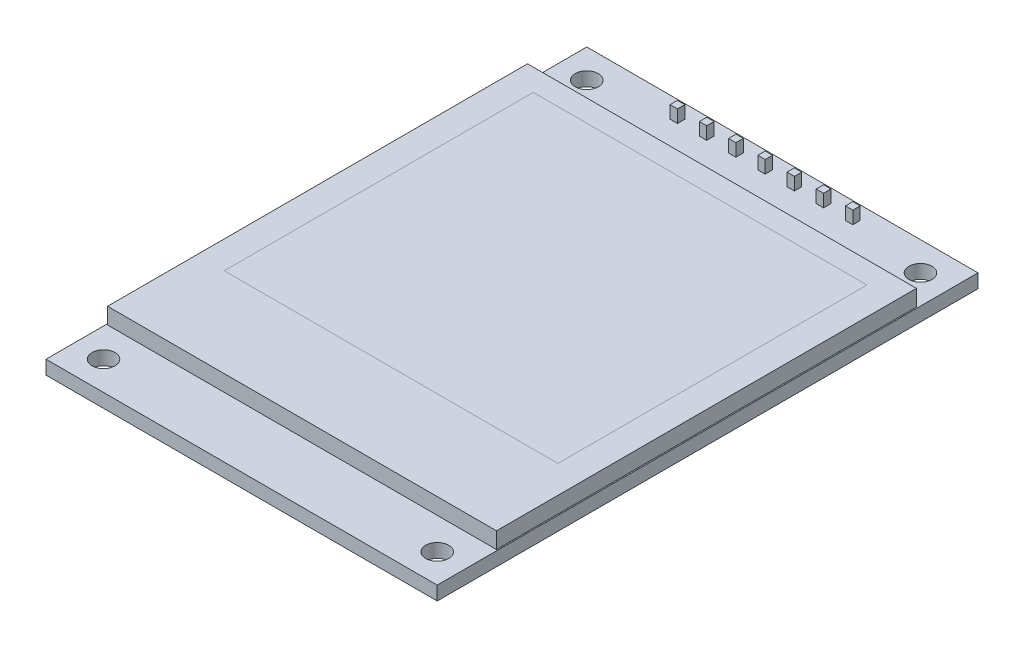
SolidWorks part; units mm, degrees
ref_plane "前视基准面" through (0, 0, 0) normal (0, 0, 1) x (1, 0, 0)
ref_plane "上视基准面" through (0, 0, 0) normal (0, 1, 0) x (1, 0, 0)
ref_plane "右视基准面" through (0, 0, 0) normal (1, 0, 0) x (0, 0, -1)
sketch "PCB底板草图" plane through (0, 0, 0) normal (0, 1, 0) x (1, 0, 0)
  line L1 (-17, -23.5) -> (17, -23.5)
  line L2 (-17, -23.5) -> (-17, 23.5)
  line L3 (-17, 23.5) -> (17, 23.5)
  line L4 (17, -23.5) -> (17, 23.5)
  circle A0 centre (-14.5, 21) radius 1
  circle A1 centre (14.5, 21) radius 1
  circle A4 centre (-14.5, -21) radius 1
  circle A5 centre (14.5, -21) radius 1
  point P0 (0, 0)
extrude "PCB底板" add sketch "PCB底板草图" along normal blind 1.2
sketch "OLED草图" plane through (0, 1.2, 0) normal (0, 1, 0) x (1, 0, 0)
  line L1 (17, 23.5) -> (-17, 23.5) construction
  line L3 (-17, 0) -> (-16.9, 0)
  line L4 (-17, 23.5) -> (-17, -23.5) construction
  line L6 (-16.9, 18.25) -> (-16.9, -18.25)
  line L7 (17, -23.5) -> (17, 23.5) construction
  line L9 (-16.9, -18.25) -> (16.9, -18.25)
  line L11 (16.9, 18.25) -> (16.9, -18.25)
  line L12 (-16.9, 18.25) -> (16.9, 18.25)
  line L13 (-14.5, 16.35) -> (14.5, 16.35)
  line L14 (14.5, 16.35) -> (14.5, -10.51)
  line L15 (-14.5, 16.35) -> (-14.5, -10.51)
  line L16 (-14.5, -10.51) -> (14.5, -10.51)
  dimension "D1" = 0.1
  dimension "D2" = 0.1
  dimension "D3" = 5.25
extrude "OLED屏幕" add sketch "OLED草图" along normal blind 1.41 contours L15 L16 L14 L13 region at (0, 1.2, -2.92)
extrude "OLED黑边" add sketch "OLED草图<3>" along normal blind 1.41 separate body contours L12 L6 L9 L11 L16 L15 L13 L14 region at (0, 1.2, -17.7525)
sketch "OLED草图<3>" plane through (0, 1.2, 0) normal (0, 1, 0) x (1, 0, 0) same geometry as "OLED草图"
sketch "2.54针脚草图" plane through (0, 0, 0) normal (0, -1, 0) x (1, 0, 0)
  line L0 (17, -23.5) -> (-17, -23.5) construction
  line L2 (17, 23.5) -> (17, -23.5) construction
  line L5 (8.89, -20.73) -> (6.35, -20.73)
  line L6 (8.89, -20.73) -> (8.89, -23.27)
  line L7 (8.89, -23.27) -> (6.35, -23.27)
  line L8 (6.35, -20.73) -> (6.35, -23.27)
  line L11 (7.94, -21.68) -> (7.3, -21.68)
  line L12 (7.94, -21.68) -> (7.94, -22.32)
  line L13 (7.94, -22.32) -> (7.3, -22.32)
  line L14 (7.3, -21.68) -> (7.3, -22.32)
  line L17 (5.4, -21.68) -> (4.76, -21.68)
  line L18 (3.81, -20.73) -> (6.35, -20.73)
  line L19 (3.81, -20.73) -> (3.81, -23.27)
  line L20 (3.81, -23.27) -> (6.35, -23.27)
  line L21 (6.35, -20.73) -> (6.35, -23.27)
  line L24 (1.27, -20.73) -> (3.81, -20.73)
  line L25 (1.27, -20.73) -> (1.27, -23.27)
  line L26 (1.27, -23.27) -> (3.81, -23.27)
  line L27 (3.81, -20.73) -> (3.81, -23.27)
  line L30 (-1.27, -20.73) -> (1.27, -20.73)
  line L31 (-1.27, -20.73) -> (-1.27, -23.27)
  line L32 (-1.27, -23.27) -> (1.27, -23.27)
  line L33 (1.27, -20.73) -> (1.27, -23.27)
  line L36 (-3.81, -20.73) -> (-1.27, -20.73)
  line L37 (-3.81, -20.73) -> (-3.81, -23.27)
  line L38 (-3.81, -23.27) -> (-1.27, -23.27)
  line L39 (-1.27, -20.73) -> (-1.27, -23.27)
  line L42 (-6.35, -20.73) -> (-3.81, -20.73)
  line L43 (-6.35, -20.73) -> (-6.35, -23.27)
  line L44 (-6.35, -23.27) -> (-3.81, -23.27)
  line L45 (-3.81, -20.73) -> (-3.81, -23.27)
  line L48 (-8.89, -20.73) -> (-6.35, -20.73)
  line L49 (-8.89, -20.73) -> (-8.89, -23.27)
  line L50 (-8.89, -23.27) -> (-6.35, -23.27)
  line L51 (-6.35, -20.73) -> (-6.35, -23.27)
  line L54 (5.4, -21.68) -> (5.4, -22.32)
  line L55 (5.4, -22.32) -> (4.76, -22.32)
  line L56 (4.76, -21.68) -> (4.76, -22.32)
  line L59 (2.86, -21.68) -> (2.22, -21.68)
  line L60 (2.86, -21.68) -> (2.86, -22.32)
  line L61 (2.86, -22.32) -> (2.22, -22.32)
  line L62 (2.22, -21.68) -> (2.22, -22.32)
  line L65 (0.32, -21.68) -> (-0.32, -21.68)
  line L66 (0.32, -21.68) -> (0.32, -22.32)
  line L67 (0.32, -22.32) -> (-0.32, -22.32)
  line L68 (-0.32, -21.68) -> (-0.32, -22.32)
  line L71 (-2.22, -21.68) -> (-2.86, -21.68)
  line L72 (-2.22, -21.68) -> (-2.22, -22.32)
  line L73 (-2.22, -22.32) -> (-2.86, -22.32)
  line L74 (-2.86, -21.68) -> (-2.86, -22.32)
  line L77 (-4.76, -21.68) -> (-5.4, -21.68)
  line L78 (-4.76, -21.68) -> (-4.76, -22.32)
  line L79 (-4.76, -22.32) -> (-5.4, -22.32)
  line L80 (-5.4, -21.68) -> (-5.4, -22.32)
  line L83 (-7.3, -21.68) -> (-7.94, -21.68)
  line L84 (-7.3, -21.68) -> (-7.3, -22.32)
  line L85 (-7.3, -22.32) -> (-7.94, -22.32)
  line L86 (-7.94, -21.68) -> (-7.94, -22.32)
  point P2 (7.62, -20.73)
  point P17 (5.08, -22)
  point P34 (2.54, -22)
  point P43 (-2.54, -22)
  point P48 (-5.08, -22)
  point P53 (-7.62, -22)
  dimension "D1" = 2.77
  dimension "D2" = 10.65
extrude "2.54针脚0" add sketch "2.54针脚草图" along normal blind 2.5 contours L5 L8 L7 L6 L14 L11 L12 L13 | L19 L20 L8 L18 L56 L17 L54 L55 | L25 L26 L19 L24 L62 L59 L60 L61 | L31 L32 L25 L30 L68 L65 L66 L67 | L37 L38 L31 L36 L74 L71 L72 L73 | L43 L44 L37 L42 L80 L77 L78 L79 | L49 L50 L43 L48 L86 L83 L84 L85 region at (8.8541, 0, -22) region at (6.3141, 0, -22) region at (3.7741, 0, -22) region at (1.2341, 0, -22) region at (-1.3059, 0, -22) region at (-3.8459, 0, -22) region at (-6.3859, 0, -22)
extrude "2.54针脚1" add sketch "2.54针脚草图<3>" along normal blind 9 and the other way blind 2.3 contours L11 L14 L13 L12 | L17 L56 L55 L54 | L65 L68 L67 L66 | L71 L74 L73 L72 | L77 L80 L79 L78 | L83 L86 L85 L84 | L62 L61 L60 L59 region at (7.62, 0, -22) region at (5.08, 0, -22) region at (0, 0, -22) region at (-2.54, 0, -22) region at (-5.08, 0, -22) region at (-7.62, 0, -22)
sketch "2.54针脚草图<3>" plane through (0, 0, 0) normal (0, -1, 0) x (1, 0, 0) same geometry as "2.54针脚草图"
